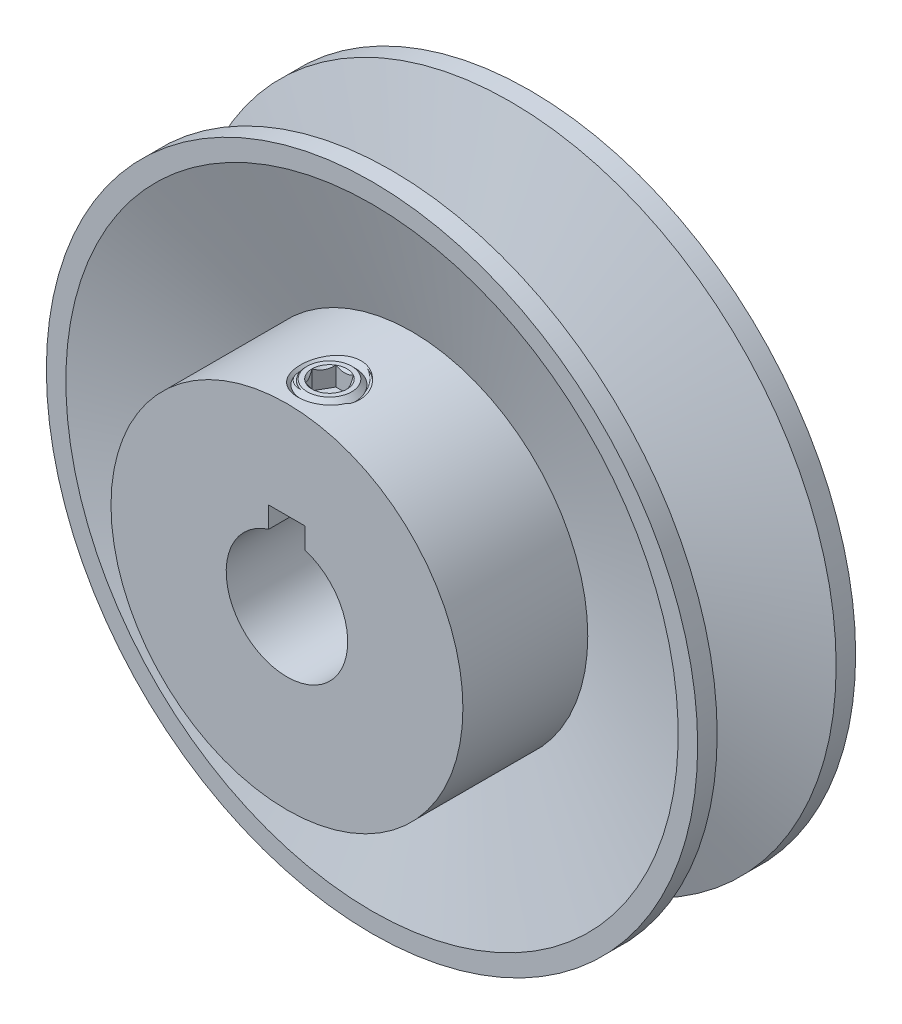
SolidWorks part; units mm, degrees
ref_plane "Front Plane" through (0, 0, 0) normal (0, 0, 1) x (1, 0, 0)
ref_plane "Top Plane" through (0, 0, 0) normal (0, 1, 0) x (1, 0, 0)
ref_plane "Right Plane" through (0, 0, 0) normal (1, 0, 0) x (0, 0, -1)
sketch "Sketch1" plane through (0, 0, 0) normal (1, 0, 0) x (0, 0, -1)
  line L0 (-21.4312, 0) -> (10.3188, 0) construction
  line L1 (-7.7724, 42.545) -> (7.7724, 42.545) construction
  line L2 (7.7724, 42.545) -> (10.3187, 42.545)
  line L5 (-10.3187, 42.545) -> (10.3187, 42.545) construction
  line L7 (-10.3187, 0) -> (-10.3187, 22.987)
  line L9 (-10.3187, 39.9986) -> (-5.1178, 22.987)
  line L13 (-7.7724, 42.545) -> (-2.9189, 26.67)
  line L14 (-2.9189, 26.67) -> (2.9189, 26.67)
  line L15 (2.9189, 26.67) -> (7.7724, 42.545)
  line L16 (10.3188, 7.9375) -> (-21.4312, 7.9375) construction
  line L17 (0, 42.545) -> (0, 0) construction
  line L18 (-7.7724, 42.545) -> (-10.3187, 42.545)
  line L20 (-21.4312, 0) -> (-21.4312, 7.9375) construction
  line L22 (4.8603, 33.02) -> (-4.8603, 33.02) construction
  line L23 (10.3187, 42.545) -> (10.3188, 0) construction
  line L24 (-5.1178, 22.987) -> (-10.3187, 22.987)
  line L26 (-10.3187, 0) -> (6.35, 0)
  line L27 (6.35, 16.637) -> (3.1764, 16.637)
  line L28 (3.1764, 16.637) -> (10.3187, 39.9986)
  line L29 (-10.3187, 39.9986) -> (-10.3187, 42.545)
  line L31 (10.3187, 39.9986) -> (10.3187, 42.545)
  line L32 (6.35, 0) -> (6.35, 16.637)
  line L33 (10.3187, 42.545) -> (10.3188, 0) construction
  line L34 (-21.4312, 22.987) -> (-21.4312, -22.987) construction
  line L35 (6.4134, 38.1) -> (-6.4134, 38.1) construction
  point P16 (0, 26.67)
  point P38 (-10.3187, 0)
revolve "Revolve1" add sketch "Sketch1" angle 360 about L0
sketch "Sketch2" plane through (0, 0, 0) normal (1, 0, 0) x (0, 0, -1)
  line L0 (10.3188, 0) -> (-21.4312, 0) construction
  line L3 (-10.3187, 0) -> (-10.3187, 22.987)
  line L4 (-10.3187, 22.987) -> (-21.4312, 22.987)
  line L5 (-21.4312, 22.987) -> (-21.4312, 0)
  line L8 (-21.4312, 0) -> (-10.3187, 0)
revolve "Revolve2" add sketch "Sketch2" angle 360 about L0
sketch "Sketch3" plane through (0, 0, 21.4312) normal (0, 0, -1) x (-1, 0, 0)
  line L0 (-2.3813, 7.9375) -> (2.3813, 7.9375) construction
  line L1 (-2.3813, 10.3188) -> (2.3813, 10.3188) construction
  line L2 (-2.3813, 10.3188) -> (-2.3813, 5.5563) construction
  line L3 (-2.3813, 5.5563) -> (2.3813, 5.5563) construction
  line L4 (2.3813, 10.3188) -> (2.3813, 5.5563) construction
  circle A0 centre (0, 0) radius 7.9375
  circle A1 centre (0, 0) radius 33.02 construction
  circle A2 centre (0, 0) radius 38.1 construction
  dimension "Keyway Wd." = 4.7625
  dimension "Keyway Dp." = 2.3813
extrude "Cut-Extrude1" cut sketch "Sketch3" along normal up to vertex (31.75 mm away) up to point (0, 0, -10.3188)
sketch "Sketch4" plane through (0, 0, 21.4312) normal (0, 0, -1) x (-1, 0, 0)
  line L0 (-2.3813, 10.3188) -> (-2.3813, 5.5563) construction
  line L1 (-2.3813, 10.3188) -> (2.3813, 10.3188) construction
  line L2 (2.3813, 10.3188) -> (2.3813, 5.5563) construction
  line L3 (-2.3813, 5.5563) -> (2.3813, 5.5563) construction
  line L4 (-2.3813, 10.3188) -> (-2.3813, 5.5563)
  line L5 (-2.3813, 10.3188) -> (2.3813, 10.3188)
  line L6 (2.3813, 10.3188) -> (2.3813, 5.5563)
  line L7 (-2.3813, 5.5563) -> (2.3813, 5.5563)
  line L8 (-2.3813, 7.9375) -> (2.3813, 7.9375) construction
  line L9 (-2.3813, 7.9375) -> (2.3813, 7.9375) construction
extrude "Cut-Extrude2" cut sketch "Sketch4" along normal up to vertex (31.75 mm away) up to point (0, 0, -10.3188)
ref_plane "Plane1" through (0, 22.987, 0) normal (0, 1, 0) x (-1, 0, 0)
sketch "Sketch5" plane through (0, 22.987, 0) normal (0, 1, 0) x (-1, 0, 0)
  line L0 (0, 10.3187) -> (0, 21.4312) construction
  line L7 (0, 19.8437) -> (0, 18.4326) construction
  circle A0 centre (0, 15.875) radius 3.9688 construction
  circle A1 centre (0, 15.875) radius 3.0868
  dimension "D3" = 0.8819
extrude "Cut-Extrude3" cut sketch "Sketch5" against normal up to surface (22.987 mm away) up to plane "Top Plane"
sketch "Sketch6" plane through (0, 22.987, 0) normal (0, 1, 0) x (-1, 0, 0)
  circle A0 centre (0, 15.875) radius 3.9688 construction
  circle A1 centre (0, 15.875) radius 3.9688
  point P3 (0, 19.8437)
curve "Helix/Spiral1" pitch 1.4111 height 24.3981 radius 3.9688 centre (0, 22.987, 15.875) axis (0, -1, 0) start towards (0, 0, 1)
sketch "Sketch7" plane through (0, 0, 0) normal (1, 0, 0) x (0, 0, -1)
  line L0 (-18.7744, 24.3981) -> (-18.7744, 22.987) construction
  line L1 (-18.7744, 22.987) -> (-19.9965, 23.6926) construction
  line L2 (-19.9965, 23.6926) -> (-18.7744, 24.3981) construction
  line L3 (-18.7744, 22.987) -> (-19.8437, 22.987) construction
  line L4 (-19.8437, 22.987) -> (-19.8437, 23.6044) construction
  line L5 (-19.8437, 23.6044) -> (-19.8437, 23.7807) construction
  line L6 (-18.9272, 23.0752) -> (-18.9272, 24.3099) construction
  line L7 (-19.9965, 23.6926) -> (-19.8437, 23.6926) construction
  line L8 (-18.9272, 23.6926) -> (-18.7744, 23.6926) construction
  line L9 (-18.8508, 24.354) -> (-18.8508, 23.0311)
  line L10 (-18.8508, 23.0311) -> (-19.8437, 23.6044)
  line L11 (-19.8437, 23.6044) -> (-19.8437, 23.7807)
  line L12 (-19.8437, 23.7807) -> (-18.8508, 24.354)
  point P16 (-18.8508, 23.6926)
  dimension "D1" = 1.4111
  dimension "D2" = 0.1764
sweep "Cut-Sweep1" cut profiles "Sketch7" path "Helix/Spiral1"
sketch "Sketch8" plane through (0, 22.987, 0) normal (0, 1, 0) x (-1, 0, 0)
  circle A0 centre (0, 15.875) radius 4.1215
extrude "Cut-Extrude4" cut sketch "Sketch8" against normal through all draft 45
sketch "Sketch9" plane through (0, 0, 0) normal (1, 0, 0) x (0, 0, -1)
  line L0 (-15.875, 22.987) -> (-15.875, 15.0495) construction
  line L1 (-19.8437, 16.1188) -> (-19.8437, 21.9177)
  line L2 (-15.875, 22.987) -> (-19.8437, 22.987) construction
  line L3 (-15.875, 22.987) -> (-15.875, 15.0495)
  line L4 (-15.875, 15.0495) -> (-19.8437, 15.0495) construction
  line L5 (-19.8437, 22.987) -> (-19.8437, 15.0495) construction
  line L6 (-18.7744, 22.987) -> (-19.8437, 21.9177)
  line L7 (-19.8437, 16.1188) -> (-18.7744, 15.0495)
  line L8 (-18.7744, 22.987) -> (-15.875, 22.987)
  line L9 (-18.7744, 15.0495) -> (-15.875, 15.0495)
  line L10 (-10.3187, 22.987) -> (-21.4312, 22.987) construction
  line L11 (-18.7744, 22.987) -> (-19.8437, 22.987) construction
  line L12 (-19.8437, 22.987) -> (-19.8437, 21.9177) construction
revolve "Revolve3" add sketch "Sketch9" angle 360 about L0
sketch "Sketch10" plane through (0, 22.987, 0) normal (0, 1, 0) x (-1, 0, 0)
  circle A1 centre (0, 15.875) radius 3.9688
  circle A2 centre (0, 15.875) radius 3.9688
  dimension "D1" = 0
curve "Helix/Spiral2" pitch 1.4111 height 9.3486 turns 6.625
sketch "Sketch11" plane through (0, 0, 0) normal (1, 0, 0) x (0, 0, -1)
  line L0 (-19.9965, 23.6926) -> (-19.9965, 22.2814) construction
  line L1 (-19.9965, 22.2814) -> (-18.7744, 22.987) construction
  line L2 (-18.7744, 22.987) -> (-19.9965, 23.6926) construction
  line L4 (-18.9272, 23.0752) -> (-18.9272, 22.8988)
  line L5 (-18.9272, 22.8988) -> (-19.8437, 22.3696)
  line L6 (-19.8437, 22.3696) -> (-19.8437, 23.6044)
  line L7 (-19.8437, 23.6044) -> (-18.9272, 23.0752)
sweep "Cut-Sweep2" cut profiles "Sketch11" path "Helix/Spiral2"
sketch "Sketch12" plane through (0, 22.987, 0) normal (0, 1, 0) x (1, 0, 0)
  line L1 (2.2914, -15.875) -> (1.1457, -13.8906)
  line L2 (1.1457, -13.8906) -> (-1.1457, -13.8906)
  line L3 (-1.1457, -13.8906) -> (-2.2914, -15.875)
  line L4 (-2.2914, -15.875) -> (-1.1457, -17.8594)
  line L5 (-1.1457, -17.8594) -> (1.1457, -17.8594)
  line L6 (1.1457, -17.8594) -> (2.2914, -15.875)
  circle A0 centre (0, -15.875) radius 1.9844 construction
extrude "Cut-Extrude5" cut sketch "Sketch12" against normal blind 2.4805
sketch "Sketch13" plane through (0, 22.987, 0) normal (0, 1, 0) x (1, 0, 0)
  circle A0 centre (0, -15.875) radius 2.2914
extrude "Cut-Extrude6" cut sketch "Sketch13" against normal through all draft 45
equation "\"D3@Sketch5\" = \"Set Screw Pitch@Sketch5\" * 5 / 8"
equation "\"D4@Helix/Spiral1\" = \"Set Screw Pitch@Sketch5\""
equation "\"D3@Helix/Spiral1\" = \"D4@Helix/Spiral1\" + ( \"Hub Dia.@Sketch1\" / 2 ) "
equation "\"D1@Sketch7\" = \"D4@Helix/Spiral1\""
equation "\"D2@Sketch7\" = \"D1@Sketch7\" / 8"
equation "\"Set Screw Hex@Sketch12\" = \"Set Screw Dia.@Sketch5\" / 2"
equation "\"D1@Cut-Extrude5\" = \"Set Screw Hex@Sketch12\" * 5 / 8"
equation "\"D4@Helix/Spiral2\" = \"D4@Helix/Spiral1\""
equation "\"D3@Helix/Spiral2\" = \"D4@Helix/Spiral1\" + \"Set Screw Lg.@Sketch9\""
